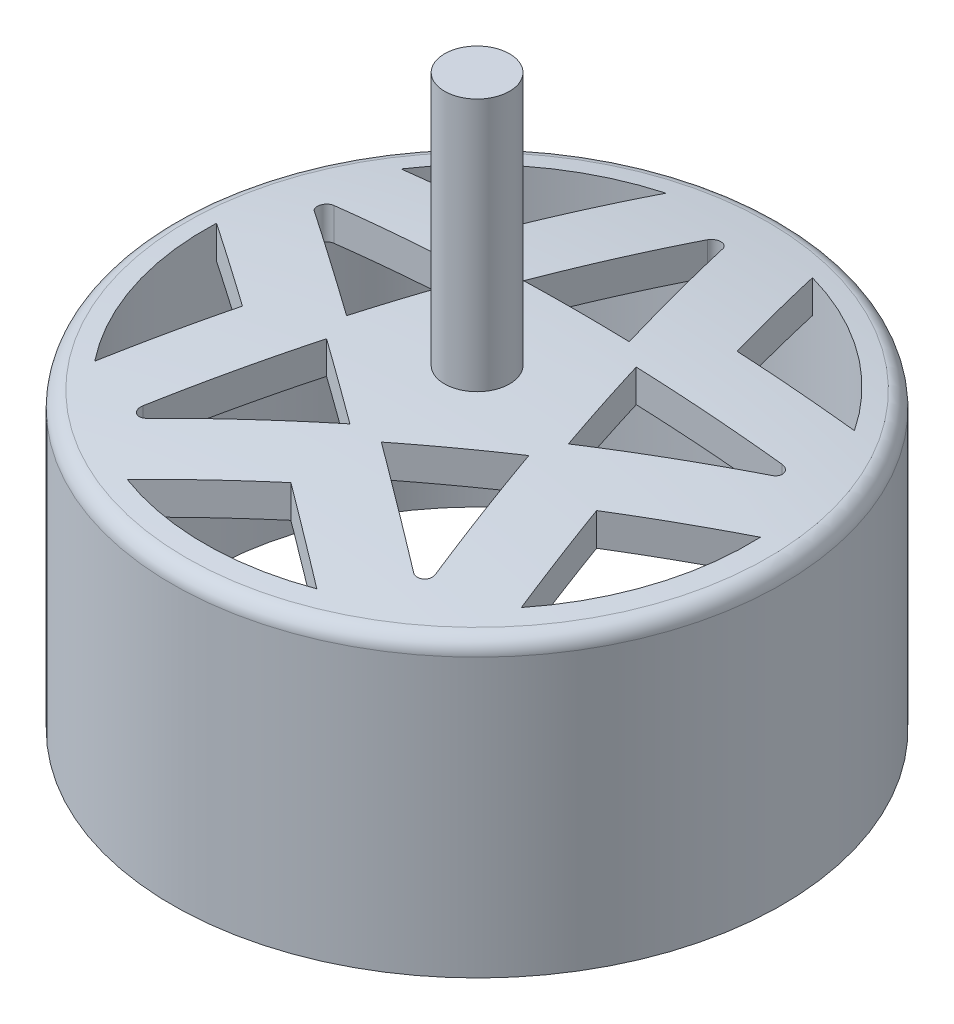
SolidWorks part; units mm, degrees
ref_plane "Front Plane" through (0, 0, 0) normal (0, 0, 1) x (1, 0, 0)
ref_plane "Top Plane" through (0, 0, 0) normal (0, 1, 0) x (1, 0, 0)
ref_plane "Right Plane" through (0, 0, 0) normal (1, 0, 0) x (0, 0, -1)
sketch "Sketch1" plane through (0, 0, 0) normal (0, 0, 1) x (1, 0, 0)
  line L0 (0, 0) -> (38350.6801, 0) construction
  line L1 (0, -0.124) -> (0, 38350.5561) construction
  line L2 (-18.75, 0) -> (-18.75, 17.9542)
  line L3 (-2, 19.4) -> (-2, 35)
  line L4 (-2, 35) -> (0, 35)
  line L7 (-16.75, 0) -> (-16.75, 16.2312)
  line L8 (-18.75, 0) -> (-16.75, 0)
  line L11 (0, 17.4165) -> (0, 35)
  arc A0 (-18.75, 17.9542) -> (-2, 19.4) centre (0, -101.5213) cw
  arc A1 (-16.75, 16.2312) -> (0, 17.4165) centre (0, -101.5213) cw
  point P17 (0, 14.9615)
  dimension "D2" = 15.6
  dimension "D5" = 120.9378
  dimension "D6" = 118.9378
  dimension "D1" = 18.75
  dimension "D3" = 19.4
  dimension "D4" = 2
  dimension "D7" = 2
revolve "Revolve1" add sketch "Sketch1" angle 360 about L1
sketch "Sketch2" plane through (0, 35, 0) normal (0, 1, 0) x (1, 0, 0)
  line L0 (-17.6336, -24.2705) -> (0, 30)
  line L1 (0, 30) -> (17.6336, -24.2705)
  line L2 (17.6336, -24.2705) -> (-28.5317, 9.2705)
  line L3 (-28.5317, 9.2705) -> (28.5317, 9.2705)
  line L4 (28.5317, 9.2705) -> (-17.6336, -24.2705)
  line L5 (0, 0) -> (0, 50000) construction
  line L6 (0, 0) -> (-50000, 0) construction
  line L7 (-40.8699, -24.2705) -> (5.6027, -24.2705) construction
  line L8 (39.8632, -24.2705) -> (-4.596, -24.2705) construction
  line L9 (0, 0) -> (0, 30) construction
  line L10 (0, 0) -> (17.6336, -24.2705) construction
  line L11 (0, 0) -> (-17.6336, -24.2705) construction
  line L12 (0, 0) -> (28.5317, 9.2705) construction
  line L13 (0, 0) -> (-28.5317, 9.2705) construction
  circle A0 centre (0, 0) radius 18.75 construction
  circle A1 centre (0, 0) radius 18.75
  circle A2 centre (0, 0) radius 16.75
  point P10 (36.6977, -39.0877)
  point P11 (0, 9.2705)
  point P16 (-17.6336, -24.2705)
  point P17 (17.6336, -24.2705)
  point P18 (30.0719, -41.3904)
  dimension "D1" = 30
  dimension "D2" = 2
extrude "Cut-Extrude3" cut sketch "Sketch2" against normal through all contours L0 A2 L3 | L2 A2 L0 | L4 A2 L2 | L1 A2 L4 | L3 A2 L1 region at (-14.0223, 35, 4.5561) region at (0, 35, 14.7439) region at (-8.6662, 35, -11.9281) region at (14.0223, 35, 4.5561) region at (8.6662, 35, -11.9281)
sketch "Sketch3" plane through (0, 35, 0) normal (0, 1, 0) x (1, 0, 0)
  line L0 (-4.5058, 16.1326) -> (-6.7354, 9.2705) construction
  line L2 (-5.8372, -15.7) -> (0, -11.459) construction
  line L3 (0, -11.459) -> (5.8372, -15.7) construction
  line L4 (13.9506, 9.2705) -> (6.7354, 9.2705) construction
  line L6 (10.8981, -3.541) -> (16.7354, 0.7) construction
  line L9 (13.1278, -10.4031) -> (10.8981, -3.541) construction
  line L10 (-14.0981, 4.0807) -> (-6.8365, -1.1951)
  line L12 (-5.8372, -15.7) -> (0, -11.459)
  line L13 (0, -11.459) -> (5.8372, -15.7)
  line L14 (-6.8365, -1.1951) -> (-4.8284, 4.9852)
  line L16 (-4.8284, 4.9852) -> (-13.8042, 4.9852)
  line L19 (-6.7354, 9.2705) -> (-13.9506, 9.2705) construction
  line L36 (-16.7354, 0.7) -> (-10.8981, -3.541) construction
  line L37 (-16.7354, 0.7) -> (-13.9506, 9.2705) construction
  line L38 (-0.4755, 14.6537) -> (-3.2492, 6.1173)
  line L39 (-3.2492, 6.1173) -> (3.2492, 6.1173)
  line L40 (3.2492, 6.1173) -> (0.4755, 14.6537)
  line L41 (4.8138, 4.9805) -> (6.8219, -1.1998)
  line L42 (6.8219, -1.1998) -> (14.0835, 4.076)
  line L43 (13.7896, 4.9805) -> (4.8138, 4.9805)
  line L44 (0.967, -6.8588) -> (6.2243, -3.0391)
  line L45 (6.2243, -3.0391) -> (8.998, -11.5756)
  line L55 (8.2285, -12.1346) -> (0.967, -6.8588)
  line L56 (-6.2243, -3.0391) -> (-0.967, -6.8588)
  line L57 (-0.967, -6.8588) -> (-8.2285, -12.1346)
  line L58 (-8.998, -11.5756) -> (-6.2243, -3.0391)
  line L59 (-13.1278, -10.4031) -> (-5.8372, -15.7) construction
  line L60 (5.8372, -15.7) -> (13.1278, -10.4031) construction
  line L61 (16.7354, 0.7) -> (13.9506, 9.2705) construction
  line L62 (-4.5058, 16.1326) -> (4.5058, 16.1326) construction
  line L64 (-10.8981, -3.541) -> (-13.1278, -10.4031) construction
  line L69 (6.7354, 9.2705) -> (4.5058, 16.1326) construction
  arc A10 (-14.0981, 4.0807) -> (-13.8042, 4.9852) centre (-13.8042, 4.4852) cw
  arc A11 (-8.2285, -12.1346) -> (-8.998, -11.5756) centre (-8.5224, -11.7301) cw
  arc A12 (8.998, -11.5756) -> (8.2285, -12.1346) centre (8.5224, -11.7301) cw
  arc A13 (14.0835, 4.076) -> (13.7896, 4.9805) centre (13.7896, 4.4805) ccw
  arc A14 (-0.4755, 14.6537) -> (0.4755, 14.6537) centre (0, 14.4992) cw
  point P12 (-15.343, 4.9852)
  point P14 (0.1434, 14.622)
  point P16 (-3.1838, 4.3821)
  point P17 (-13.9506, 4.3821)
  point P18 (13.9506, 4.3821)
  point P19 (3.1838, 4.3821)
  point P20 (-0.1434, 14.622)
  point P21 (8.4786, -11.9137)
  point P22 (5.1515, -1.6738)
  point P23 (13.862, 4.6548)
  point P24 (-8.7106, -11.7452)
  point P25 (0, -5.4166)
  point P26 (8.7106, -11.7452)
  point P27 (-13.862, 4.6548)
  point P28 (-5.1515, -1.6738)
  point P29 (-8.4786, -11.9137)
  point P33 (-15.343, 4.9852)
  point P46 (-3.1838, 2.3821)
  point P47 (-7.3313, 2.3821)
  point P49 (-7.3313, 2.3821)
  point P50 (-3.9759, -0.0558)
  point P51 (-3.2493, -2.2918)
  point P52 (-4.531, -6.2364)
  point P54 (-4.531, -6.2364)
  point P55 (-1.1756, -3.7985)
  point P56 (1.1756, -3.7985)
  point P57 (4.531, -6.2364)
  point P59 (4.531, -6.2364)
  point P60 (3.2493, -2.2918)
  point P61 (3.9759, -0.0558)
  point P62 (7.3313, 2.3821)
  point P64 (7.3313, 2.3821)
  point P65 (3.1838, 2.3821)
  point P66 (1.2817, 3.7641)
  point P67 (0, 7.7086)
  point P69 (0, 7.7086)
  point P70 (-1.2817, 3.7641)
  point P77 (0, 0)
  point P98 (-3.8244, 9.0584)
  point P99 (3.2236, 6.1962)
  point P100 (-3.2482, 6.1143)
  point P101 (2.8403, 7.3757)
  dimension "D1" = 0.5
  dimension "D3" = 0.5
  dimension "D2" = 10
  dimension "D4" = 4.29
  dimension "D5" = 4.29
  dimension "D6" = 4.29
  dimension "D7" = 4.29
  dimension "D8" = 4.29
  dimension "D9" = 4.29
  dimension "D10" = 4.29
  dimension "D11" = 4.29
extrude "Cut-Extrude7" cut sketch "Sketch3" against normal through all contours A10 L10 L14 L16 | A14 L38 L39 L40 | L42 A13 L43 L41 | A12 L45 L44 L55 | A11 L57 L56 L58 region at (-8.9232, 35, -2.8993) region at (0, 35, -9.3671) region at (8.9087, 35, -2.8946) region at (5.5059, 35, 7.5782) region at (-5.5059, 35, 7.5782)
fillet "Fillet1" radius 1 1 edges at (0, 17.9542, -18.75)
